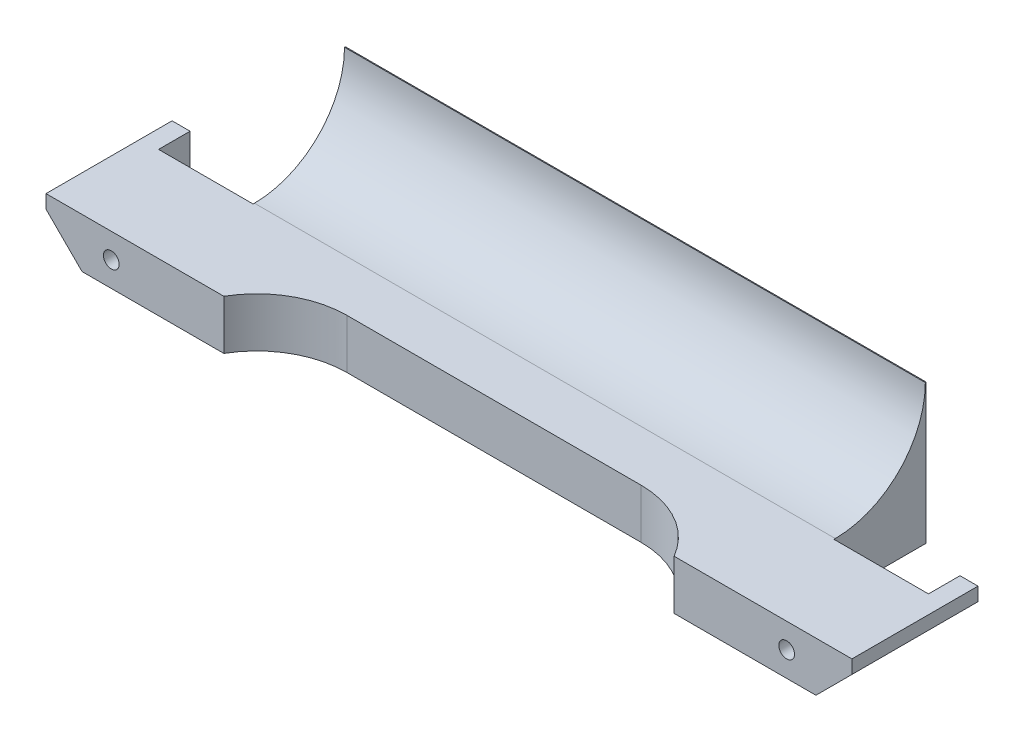
SolidWorks part; units mm, degrees
ref_plane "Top Plane" through (0, 0, 0) normal (0, 0, 1) x (1, 0, 0)
ref_plane "Front Plane" through (0, 0, 0) normal (0, 1, 0) x (1, 0, 0)
ref_plane "Right Plane" through (0, 0, 0) normal (1, 0, 0) x (0, 0, -1)
sketch "Sketch1" plane through (0, 0, 0) normal (0, 0, 1) x (1, 0, 0)
  line L1 (-64.5, -11.5) -> (64.5, -11.5)
  line L2 (-64.5, -11.5) -> (-64.5, 11.5)
  line L3 (-64.5, 11.5) -> (64.5, 11.5)
  line L4 (64.5, -11.5) -> (64.5, 11.5)
  line L5 (-64.5, -11.5) -> (64.5, 11.5) construction
  line L6 (-64.5, 11.5) -> (64.5, -11.5) construction
  point P0 (0, 0)
  dimension "D1" = 129
  dimension "D2" = 23
extrude "Boss-Extrude1" add sketch "Sketch1" along normal blind 0.2
sketch "Sketch2" plane through (0, 0, 0.2) normal (0, 0, 1) x (1, 0, 0)
  line L0 (64.5, -11.5) -> (64.5, 11.5) construction
  line L1 (-64.5, -11.5) -> (64.5, -11.5)
  line L2 (-64.5, -11.5) -> (-64.5, -8.5)
  line L3 (-64.5, -8.5) -> (64.5, -8.5)
  line L4 (64.5, -11.5) -> (64.5, -8.5)
  dimension "D1" = 3
extrude "Boss-Extrude2" add sketch "Sketch2" along normal blind 20.3
fillet "Fillet1" radius 20 1 edges at (0, -8.5, 0.2)
sketch "Sketch3" plane through (0, 0, 20.5) normal (0, 0, 1) x (1, 0, 0)
  line L0 (-64.5, -11.5) -> (64.5, -11.5) construction
  line L1 (-89.5, -8.5) -> (89.5, -8.5)
  line L2 (-89.5, -8.5) -> (-89.5, -11.5)
  line L3 (-89.5, -11.5) -> (89.5, -11.5)
  line L4 (89.5, -8.5) -> (89.5, -11.5)
  line L5 (-89.5, -8.5) -> (89.5, -11.5) construction
  line L6 (-89.5, -11.5) -> (89.5, -8.5) construction
  point P0 (0, -10)
  dimension "D1" = 179
  dimension "D2" = 3
  dimension "D3" = 0
  dimension "D4" = 0
extrude "Boss-Extrude3" add sketch "Sketch3" along normal blind 21
sketch "Sketch4" plane through (0, -11.5, 0) normal (0, -1, 0) x (1, 0, 0)
  line L1 (-89.5, 20.5) -> (-85.5, 20.5)
  line L2 (-89.5, 20.5) -> (-89.5, 13.5)
  line L3 (-89.5, 13.5) -> (-85.5, 13.5)
  line L4 (-85.5, 20.5) -> (-85.5, 13.5)
  line L5 (89.5, 20.5) -> (85.5, 20.5)
  line L6 (89.5, 20.5) -> (89.5, 13.5)
  line L7 (89.5, 13.5) -> (85.5, 13.5)
  line L8 (85.5, 20.5) -> (85.5, 13.5)
  dimension "D1" = 7
  dimension "D2" = 4
  dimension "D3" = 7
  dimension "D4" = 4
extrude "Boss-Extrude4" add sketch "Sketch4" against normal blind 3
sketch "Sketch5" plane through (0, -11.5, 0) normal (0, -1, 0) x (1, 0, 0)
  line L24 (-64.5, 0) -> (64.5, 0)
  line L25 (64.5, 0) -> (64.5, 20.5)
  line L26 (64.5, 20.5) -> (85.5, 20.5)
  line L27 (85.5, 20.5) -> (85.5, 13.5)
  line L28 (85.5, 13.5) -> (89.5, 13.5)
  line L29 (89.5, 13.5) -> (89.5, 41.5)
  line L30 (89.5, 41.5) -> (-89.5, 41.5)
  line L31 (-89.5, 41.5) -> (-89.5, 13.5)
  line L32 (-89.5, 13.5) -> (-85.5, 13.5)
  line L33 (-85.5, 13.5) -> (-85.5, 20.5)
  line L34 (-85.5, 20.5) -> (-64.5, 20.5)
  line L35 (-64.5, 20.5) -> (-64.5, 0)
  line L36 (-64.5, 0) -> (64.5, 0)
  line L37 (64.5, 0) -> (64.5, 20.5)
  line L38 (64.5, 20.5) -> (85.5, 20.5)
  line L39 (85.5, 20.5) -> (85.5, 13.5)
  line L40 (85.5, 13.5) -> (89.5, 13.5)
  line L41 (89.5, 13.5) -> (89.5, 41.5)
  line L42 (89.5, 41.5) -> (-89.5, 41.5)
  line L43 (-89.5, 41.5) -> (-89.5, 13.5)
  line L44 (-89.5, 13.5) -> (-85.5, 13.5)
  line L45 (-85.5, 13.5) -> (-85.5, 20.5)
  line L46 (-85.5, 20.5) -> (-64.5, 20.5)
  line L47 (-64.5, 20.5) -> (-64.5, 0)
  dimension "D1" = 0
extrude "Boss-Extrude5" add sketch "Sketch5" along normal blind 8
chamfer "Chamfer1" distance 8 angle 45 2 edges at (89.5, -19.5, 27.5) (-89.5, -19.5, 27.5)
sketch "Sketch6" plane through (0, 0, 41.5) normal (0, 0, 1) x (1, 0, 0)
  line L2 (81.5, -19.5) -> (-81.5, -19.5) construction
  circle A0 centre (-75, -14) radius 1.75
  circle A1 centre (75, -14) radius 1.75
  point P6 (-38.8438, -17.8687)
  dimension "D2" = 75
  dimension "D3" = 5.5
  dimension "D4" = 5.5
  dimension "D5" = 3.5
  dimension "D6" = 3.5
  dimension "D1" = 150
extrude "Cut-Extrude1" cut sketch "Sketch6" against normal through all
sketch "Sketch7" plane through (0, 0, 41.5) normal (0, 0, 1) x (1, 0, 0)
  line L0 (89.5, -8.5) -> (-89.5, -8.5) construction
  line L1 (-50, -8.5) -> (50, -8.5)
  line L2 (-50, -8.5) -> (-50, -19.5)
  line L3 (-50, -19.5) -> (50, -19.5)
  line L4 (50, -8.5) -> (50, -19.5)
  line L5 (81.5, -19.5) -> (-81.5, -19.5) construction
  dimension "D1" = 100
  dimension "D2" = 50
extrude "Cut-Extrude2" cut sketch "Sketch7" against normal blind 10
fillet "Fillet2" radius 20 2 edges at (50, -14, 31.5) (-50, -14, 31.5)
